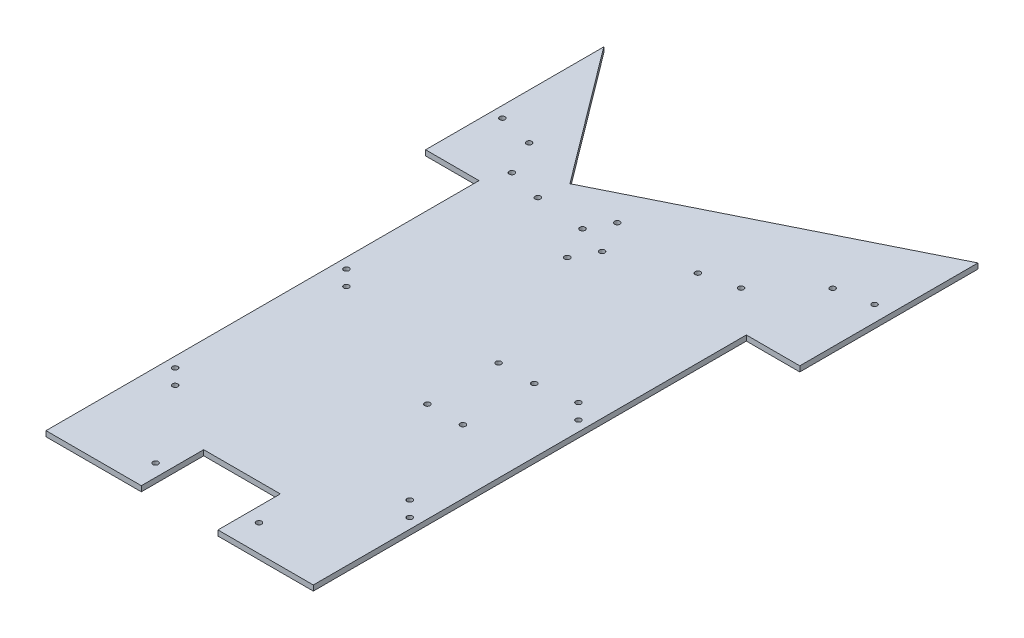
SolidWorks part; units mm, degrees
ref_plane "Front Plane" through (0, 0, 0) normal (0, 0, 1) x (1, 0, 0)
ref_plane "Top Plane" through (0, 0, 0) normal (0, 1, 0) x (1, 0, 0)
ref_plane "Right Plane" through (0, 0, 0) normal (1, 0, 0) x (0, 0, -1)
sketch "Sketch1" plane through (0, 0, 0) normal (0, 1, 0) x (1, 0, 0)
  line L0 (0, -55) -> (0, 55) construction
  line L2 (-75, -100) -> (-75, 100)
  line L3 (-75, 100) -> (75, 100)
  line L4 (75, -100) -> (75, 100)
  line L5 (-75, -100) -> (75, 100) construction
  line L6 (-75, 100) -> (75, -100) construction
  line L8 (-21.5, -100) -> (-21.5, -65)
  line L9 (-21.5, -65) -> (21.5, -65)
  line L10 (21.5, -100) -> (21.5, -65)
  line L11 (-75, -100) -> (-21.5, -100)
  line L12 (21.5, -100) -> (75, -100)
  circle A0 centre (-69.2426, 62.7961) radius 1.5
  circle A1 centre (-60.7574, 54.3108) radius 1.5
  circle A2 centre (60.7574, 63.0348) radius 1.5
  circle A3 centre (69.2426, 54.5495) radius 1.5
  circle A4 centre (-69.2426, -33.2742) radius 1.5
  circle A5 centre (-60.7574, -41.7595) radius 1.5
  circle A6 centre (60.7574, -31.6419) radius 1.5
  circle A7 centre (69.2426, -40.1271) radius 1.5
  circle A8 centre (19.1, 59.876) radius 1.5
  circle A10 centre (39.1, 19.876) radius 1.5
  circle A11 centre (19.1, 19.876) radius 1.5
  circle A12 centre (39.1, 59.876) radius 1.5
  circle A13 centre (-28.5, -85) radius 1.5
  circle A14 centre (29.5, -85) radius 1.5
  point P0 (0, 0)
  point P46 (0, -65)
  dimension "D5" = 3
  dimension "D6" = 3
  dimension "D11" = 58
  dimension "D1" = 150
  dimension "D2" = 200
  dimension "D3" = 35
  dimension "D4" = 43
  dimension "D7" = 15
  dimension "D8" = 15
  dimension "D9" = 8
extrude "Boss-Extrude1" add sketch "Sketch1" along normal blind 3
sketch "Sketch2" plane through (0, 3, 0) normal (0, 1, 0) x (1, 0, 0)
  line L8 (-75, 100) -> (-75, 143)
  line L9 (-75, 143) -> (-105, 143)
  line L10 (-105, 143) -> (-105, 243)
  line L11 (-105, 243) -> (-48, 167)
  line L12 (-48, 167) -> (105, 243)
  line L13 (105, 243) -> (105, 143)
  line L14 (105, 143) -> (75, 143)
  line L15 (75, 143) -> (75, 100)
  line L20 (-75, 100) -> (75, 100)
  circle A0 centre (-12.8714, 130.3772) radius 1.5
  circle A1 centre (-6.0318, 143.0744) radius 1.5
  circle A2 centre (-15.7372, 161.3276) radius 1.5
  circle A3 centre (-22.5768, 148.6304) radius 1.5
  circle A4 centre (31.34, 159.4445) radius 1.5
  circle A5 centre (50.7426, 164.2965) radius 1.5
  circle A6 centre (76.5366, 189.8832) radius 1.5
  circle A7 centre (96.1557, 193.7679) radius 1.5
  circle A8 centre (-50.2701, 151.2364) radius 1.5
  circle A9 centre (-69.6726, 156.0884) radius 1.5
  circle A10 centre (-79.3212, 175.4165) radius 1.5
  circle A11 centre (-98.8125, 179.8985) radius 1.5
  dimension "D2" = 100
  dimension "D3" = 27
  dimension "D4" = 30
  dimension "D1" = 43
  dimension "D5" = 24
extrude "Boss-Extrude3" add sketch "Sketch2" against normal blind 3
